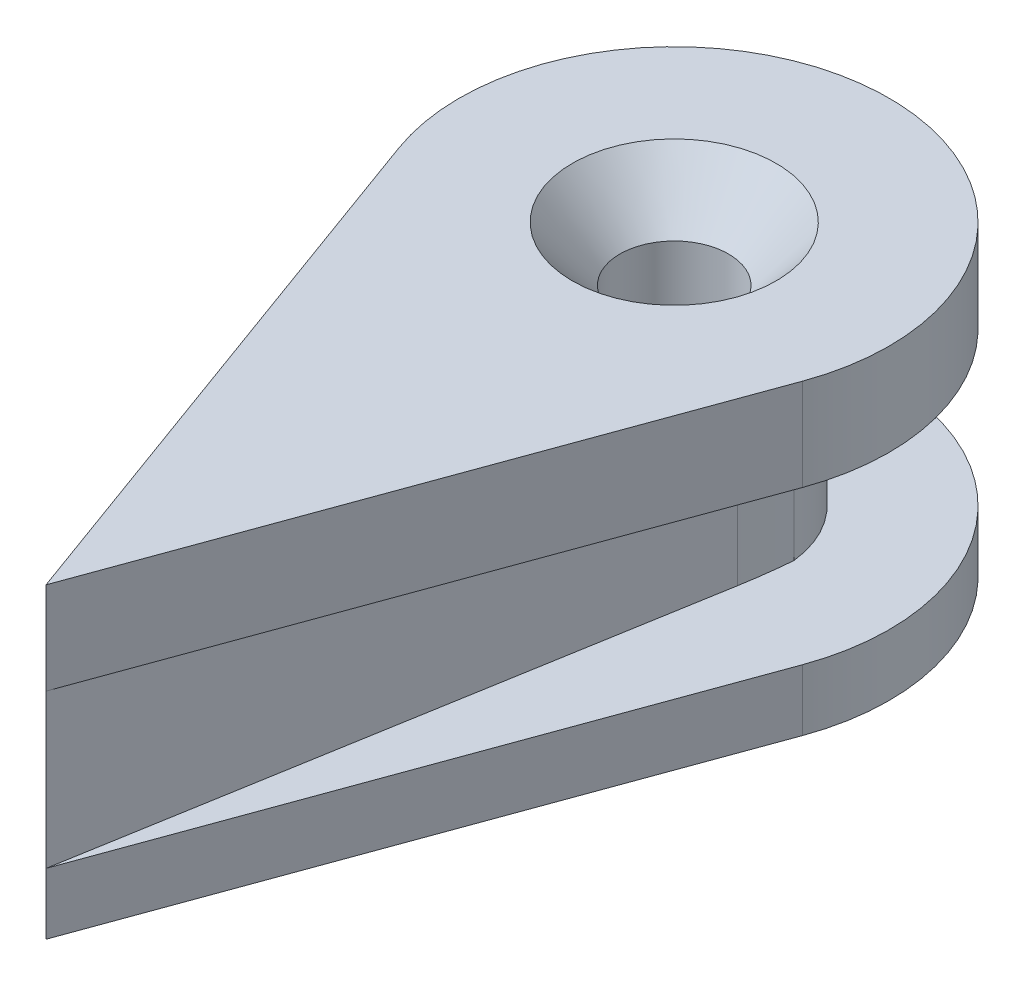
SolidWorks part; units mm, degrees
ref_plane "Front Plane" through (0, 0, 0) normal (0, 0, 1) x (1, 0, 0)
ref_plane "Top Plane" through (0, 0, 0) normal (0, 1, 0) x (1, 0, 0)
ref_plane "Right Plane" through (0, 0, 0) normal (1, 0, 0) x (0, 0, -1)
sketch "Sketch1" plane through (0, 0, 0) normal (0, 1, 0) x (1, 0, 0)
  line L0 (8.3539, -3.0406) -> (0, -25.9926)
  line L1 (0, -25.9926) -> (-8.3539, -3.0406)
  circle A0 centre (0, 0) radius 8.89
  dimension "D1" = 17.78
  dimension "D2" = 40
extrude "Boss-Extrude1" add sketch "Sketch1" along normal blind 12.7 contours A0 | A0 L1 L0
sketch "Sketch2" plane through (0, 0, 0) normal (0, 0, 1) x (1, 0, 0)
  line L0 (8.89, 0) -> (8.89, 12.7) construction
  line L1 (2.9908, 8.255) -> (8.89, 8.255)
  line L2 (2.9908, 8.255) -> (2.9909, 4.445)
  line L3 (2.9909, 4.445) -> (8.89, 4.445)
  line L4 (8.89, 8.255) -> (8.89, 4.445)
  line L5 (0, 0) -> (0, 12.7) construction
  line L6 (0, 6.35) -> (-8.89, 6.35) construction
  line L7 (-8.89, 12.7) -> (-8.89, 0) construction
  line L8 (-8.89, 8.255) -> (-8.89, 4.445)
  line L9 (-2.9908, 4.445) -> (-8.89, 4.445)
  line L10 (-2.9908, 8.255) -> (-2.9908, 4.445)
  line L11 (-2.9908, 8.255) -> (-8.89, 8.255)
  dimension "D1" = 3.81
  dimension "D2" = 2.9908
extrude "Cut-Extrude1" [suppressed] cut sketch "Sketch2" against normal through all and the other way through all
sketch "Sketch5" plane through (0, 12.7, 0) normal (0, 1, 0) x (1, 0, 0)
  line L0 (-4.445, 0.5129) -> (-4.445, 0)
  line L1 (4.445, 0.5129) -> (4.445, 0)
  line L2 (0, 8.89) -> (0, -25.9926) construction
  line L3 (4.445, 0) -> (0, -25.9926)
  line L4 (0, -25.9926) -> (-4.445, 0)
  line L5 (-17.2822, 11.43) -> (15.9969, 11.43)
  line L6 (15.9969, 11.43) -> (0, -25.9926)
  line L8 (-17.2822, 11.43) -> (0, -25.9926)
  arc A0 (8.3539, -3.0406) -> (-8.3539, -3.0406) centre (0, 0) ccw construction
  arc A1 (-4.445, 0.5129) -> (4.445, 0.5129) centre (0, 0) cw
  arc M3 (8.3539, -3.0406) -> (-8.3539, -3.0406) centre (0, 0) ccw
  line M4 (-8.3539, -3.0406) -> (0, -25.9926)
  dimension "D1" = 8.89
  dimension "D2" = 2.54
extrude "Cut-Extrude2" cut sketch "Sketch5" against normal blind 6.35 from offset 3.81 contours L4 L0 M4 M3 offset against normal yes
hole_wizard "CSK for #8 Flat Head Machine Screw1" positions "Sketch4" profile "Sketch3" countersink size "#8" standard "ANSI Inch" end condition up to next
sketch "Sketch4" plane through (0, 12.7, 0) normal (0, 1, 0) x (1, 0, 0)
  point P0 (0, 0)
sketch "Sketch3" plane through (0, 12.7, 0) normal (1, 0, 0) x (0, 0, 1)
  line L0 (0, 0) -> (0, 12.7)
  line L1 (0, 12.7) -> (2.2479, 12.7)
  line L2 (2.2479, 12.7) -> (2.2479, 2.2645)
  line L3 (2.2479, 2.2645) -> (4.2164, 0)
  line L5 (4.2164, 0) -> (0, 0)
  line L6 (-2.2479, 2.2645) -> (-4.2164, 0) construction
  line L11 (0, -6.35) -> (0, 107.95) construction
  dimension "Thru Hole Dia." = 4.4958
  dimension "Thru Hole Depth" = 12.7
  dimension "Near C'Sink Dia." = 8.4328
  dimension "Near C'Sink Angle" = 82
mirror "Mirror1" about plane through (0, 0, 0) normal (1, 0, 0) of "Cut-Extrude2"
fillet "Fillet1" radius 25.4 2 edges at (-4.445, 5.715, 0) (4.445, 5.715, 0)
